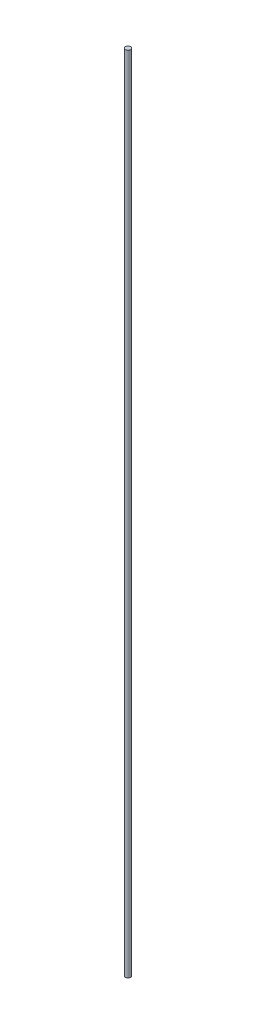
SolidWorks part; units mm, degrees
ref_plane "Front Plane" through (0, 0, 0) normal (0, 0, 1) x (1, 0, 0)
ref_plane "Top Plane" through (0, 0, 0) normal (0, 1, 0) x (1, 0, 0)
ref_plane "Right Plane" through (0, 0, 0) normal (1, 0, 0) x (0, 0, -1)
sketch "Sketch1" plane through (0, 0, 0) normal (0, 0, 1) x (1, 0, 0)
  line L0 (0, 0) -> (0, 1949.196)
  dimension "D1" = 1949.196
sweep "Sweep1" add path "Sketch1" circular profile diameter 12.7 parameters "D3"=12.7
